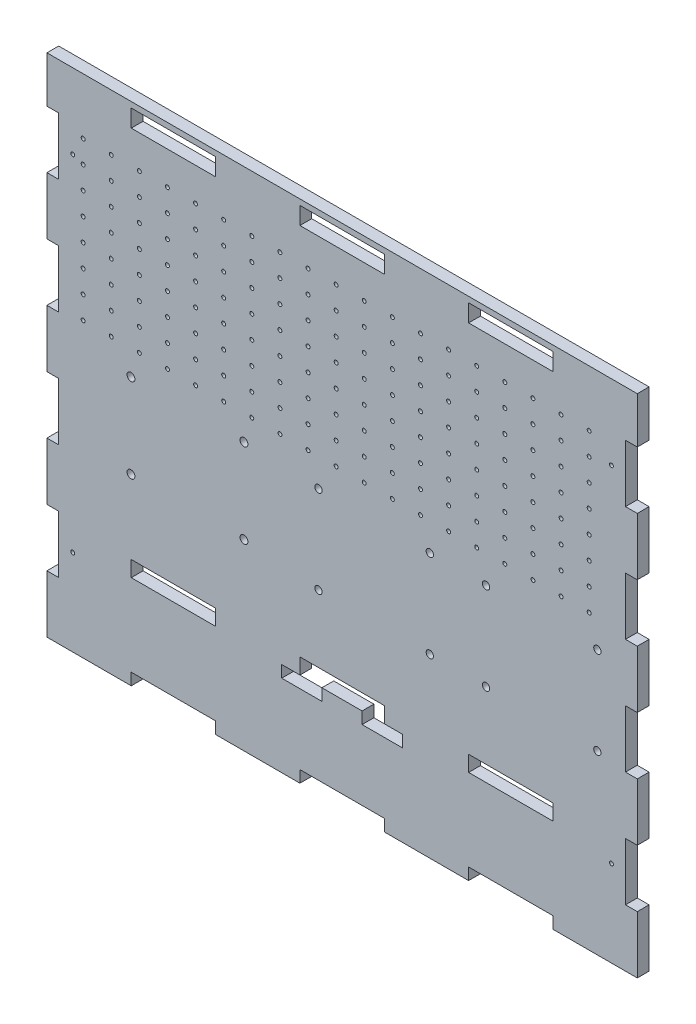
SolidWorks part; units mm, degrees
ref_plane "Front Plane" through (0, 0, 0) normal (0, 0, 1) x (1, 0, 0)
ref_plane "Top Plane" through (0, 0, 0) normal (0, 1, 0) x (1, 0, 0)
ref_plane "Right Plane" through (0, 0, 0) normal (1, 0, 0) x (0, 0, -1)
sketch "Sketch1" plane through (0, 0, 0) normal (0, 0, 1) x (1, 0, 0)
  line L1 (-127.8759, 139.2641) -> (138.8241, 139.2641)
  line L2 (-127.8759, 139.2641) -> (-127.8759, -84.2559)
  line L3 (-127.8759, -84.2559) -> (138.8241, -84.2559)
  line L4 (138.8241, 139.2641) -> (138.8241, -84.2559)
  dimension "D1" = 266.7
  dimension "D2" = 223.52
extrude "Boss-Extrude1" add sketch "Sketch1" along normal blind 5.334
sketch "Sketch2" plane through (0, 0, 5.334) normal (0, 0, 1) x (1, 0, 0)
  line L0 (-127.8759, -84.2559) -> (138.8241, -84.2559) construction
  line L1 (-89.7759, -84.2559) -> (-51.6759, -84.2559)
  line L2 (-89.7759, -84.2559) -> (-89.7759, -78.9219)
  line L3 (-89.7759, -78.9219) -> (-51.6759, -78.9219)
  line L4 (-51.6759, -84.2559) -> (-51.6759, -78.9219)
  line L5 (-89.7759, -78.9219) -> (-127.8759, -78.9219) construction
  line L6 (-13.5759, -84.2559) -> (24.5241, -84.2559)
  line L7 (-13.5759, -84.2559) -> (-13.5759, -78.9219)
  line L8 (-13.5759, -78.9219) -> (24.5241, -78.9219)
  line L9 (24.5241, -84.2559) -> (24.5241, -78.9219)
  line L10 (62.6241, -84.2559) -> (100.7241, -84.2559)
  line L11 (62.6241, -84.2559) -> (62.6241, -78.9219)
  line L12 (62.6241, -78.9219) -> (100.7241, -78.9219)
  line L13 (100.7241, -84.2559) -> (100.7241, -78.9219)
  line L14 (-127.8759, 139.2641) -> (-127.8759, -84.2559) construction
  line L15 (-51.6759, -78.9219) -> (-13.5759, -78.9219) construction
  line L16 (24.5241, -78.9219) -> (62.6241, -78.9219) construction
  line L17 (62.6241, -78.9219) -> (62.364, -79.7896) construction
  line L18 (100.7241, -78.9219) -> (138.8241, -78.9219) construction
  line L19 (138.8241, -84.2559) -> (138.8241, 139.2641) construction
  line L20 (-127.8759, 27.5041) -> (138.8241, 27.5041) construction
  line L21 (100.7241, 139.2641) -> (100.7241, 133.9301)
  line L22 (62.6241, 133.9301) -> (100.7241, 133.9301)
  line L23 (62.6241, 139.2641) -> (62.6241, 133.9301)
  line L24 (24.5241, 139.2641) -> (24.5241, 133.9301)
  line L25 (-13.5759, 133.9301) -> (24.5241, 133.9301)
  line L26 (-13.5759, 139.2641) -> (-13.5759, 133.9301)
  line L27 (-51.6759, 139.2641) -> (-51.6759, 133.9301)
  line L28 (-89.7759, 133.9301) -> (-51.6759, 133.9301)
  line L29 (-89.7759, 139.2641) -> (-89.7759, 133.9301)
  line L30 (62.6241, 139.2641) -> (100.7241, 139.2641)
  line L31 (-13.5759, 139.2641) -> (24.5241, 139.2641)
  line L32 (-89.7759, 139.2641) -> (-51.6759, 139.2641)
  dimension "D1" = 5.334
extrude "Cut-Extrude1" cut sketch "Sketch2" against normal through all
sketch "Sketch5" plane through (0, 0, 5.334) normal (0, 0, 1) x (1, 0, 0)
  line L0 (-51.6759, -34.8224) -> (-13.5759, -34.8224) construction
  line L1 (-89.7759, -34.8224) -> (-51.6759, -34.8224)
  line L2 (-89.7759, -34.8224) -> (-89.7759, -41.9344)
  line L3 (-89.7759, -41.9344) -> (-51.6759, -41.9344)
  line L4 (-51.6759, -34.8224) -> (-51.6759, -41.9344)
  line L5 (-13.5759, -34.8224) -> (24.5241, -34.8224)
  line L6 (-13.5759, -34.8224) -> (-13.5759, -41.9344)
  line L7 (-13.5759, -41.9344) -> (24.5241, -41.9344)
  line L8 (24.5241, -34.8224) -> (24.5241, -41.9344)
  line L9 (62.6241, -34.8224) -> (100.7241, -34.8224)
  line L10 (62.6241, -34.8224) -> (62.6241, -41.9344)
  line L11 (62.6241, -41.9344) -> (100.7241, -41.9344)
  line L12 (100.7241, -34.8224) -> (100.7241, -41.9344)
  line L13 (-51.6759, -41.9344) -> (-13.5759, -41.9344) construction
  line L14 (24.5241, -34.8224) -> (62.6241, -34.8224) construction
  line L15 (24.5241, -41.9344) -> (62.6241, -41.9344) construction
  line L16 (-89.7759, -34.8224) -> (-127.8759, -34.8224) construction
  line L17 (-127.8759, 139.2641) -> (-127.8759, -84.2559) construction
  line L18 (-89.7759, -41.9344) -> (-127.8759, -41.9344) construction
  line L19 (100.7241, -34.8224) -> (138.8241, -34.8224) construction
  line L20 (138.8241, -84.2559) -> (138.8241, 139.2641) construction
  line L21 (100.7241, -41.9344) -> (138.8241, -41.9344) construction
  dimension "D1" = 7.112
extrude "Cut-Extrude3" cut sketch "Sketch5" against normal through all
sketch "Sketch8" plane through (0, 0, 5.334) normal (0, 0, 1) x (1, 0, 0)
  line L0 (-13.5759, -41.9344) -> (24.5241, -41.9344) construction
  line L1 (-21.7977, -47.2684) -> (-3.6478, -47.2684)
  line L2 (-21.7977, -47.2684) -> (-21.7977, -41.9344)
  line L3 (-21.7977, -41.9344) -> (-3.6478, -41.9344)
  line L4 (-3.6478, -47.2684) -> (-3.6478, -41.9344)
  line L5 (-3.6478, -47.2684) -> (14.5022, -47.2684) construction
  line L6 (14.5022, -41.9344) -> (32.6521, -41.9344)
  line L7 (14.5022, -41.9344) -> (14.5022, -47.2684)
  line L8 (14.5022, -47.2684) -> (32.6521, -47.2684)
  line L9 (32.6521, -41.9344) -> (32.6521, -47.2684)
  line L10 (14.5022, -47.2684) -> (14.3218, -49.4005) construction
  line L11 (14.5022, -41.9344) -> (-3.6478, -41.9344) construction
  line L12 (62.6241, -34.8224) -> (62.6241, -41.9344) construction
  line L13 (-51.6759, -41.9344) -> (-51.6759, -34.8224) construction
  dimension "D1" = 5.334
  dimension "D2" = 29.972
  dimension "D3" = 29.8782
extrude "Cut-Extrude6" cut sketch "Sketch8" against normal through all
sketch "Sketch9" plane through (0, 0, 5.334) normal (0, 0, 1) x (1, 0, 0)
  line L0 (-111.5143, 118.9789) -> (-98.8143, 118.9789) construction
  line L1 (-111.5143, 108.8189) -> (-98.8143, 108.8189) construction
  line L2 (-111.5143, 98.6589) -> (-98.8143, 98.6589) construction
  line L3 (-111.5143, 88.4989) -> (-98.8143, 88.4989) construction
  line L4 (-111.5143, 78.3389) -> (-98.8143, 78.3389) construction
  line L5 (-111.5143, 68.1789) -> (-98.8143, 68.1789) construction
  line L6 (-111.5143, 58.0189) -> (-98.8143, 58.0189) construction
  line L7 (-111.5143, 47.8589) -> (-98.8143, 47.8589) construction
  line L8 (-111.5143, 118.9789) -> (-111.5143, 108.8189) construction
  circle A0 centre (-111.5143, 118.9789) radius 0.889
  circle A1 centre (-98.8143, 118.9789) radius 0.889
  circle A2 centre (-86.1143, 118.9789) radius 0.889
  circle A3 centre (-73.4143, 118.9789) radius 0.889
  circle A4 centre (-60.7143, 118.9789) radius 0.889
  circle A5 centre (-48.0143, 118.9789) radius 0.889
  circle A6 centre (-35.3143, 118.9789) radius 0.889
  circle A7 centre (-22.6143, 118.9789) radius 0.889
  circle A8 centre (-9.9143, 118.9789) radius 0.889
  circle A9 centre (2.7857, 118.9789) radius 0.889
  circle A10 centre (15.4857, 118.9789) radius 0.889
  circle A11 centre (28.1857, 118.9789) radius 0.889
  circle A12 centre (40.8857, 118.9789) radius 0.889
  circle A13 centre (53.5857, 118.9789) radius 0.889
  circle A14 centre (66.2857, 118.9789) radius 0.889
  circle A15 centre (78.9857, 118.9789) radius 0.889
  circle A16 centre (91.6857, 118.9789) radius 0.889
  circle A17 centre (104.3857, 118.9789) radius 0.889
  circle A18 centre (117.0857, 118.9789) radius 0.889
  circle A19 centre (-111.5143, 108.8189) radius 0.889
  circle A20 centre (-98.8143, 108.8189) radius 0.889
  circle A21 centre (-86.1143, 108.8189) radius 0.889
  circle A22 centre (-73.4143, 108.8189) radius 0.889
  circle A23 centre (-60.7143, 108.8189) radius 0.889
  circle A24 centre (-48.0143, 108.8189) radius 0.889
  circle A25 centre (-35.3143, 108.8189) radius 0.889
  circle A26 centre (-22.6143, 108.8189) radius 0.889
  circle A27 centre (-9.9143, 108.8189) radius 0.889
  circle A28 centre (2.7857, 108.8189) radius 0.889
  circle A29 centre (15.4857, 108.8189) radius 0.889
  circle A30 centre (28.1857, 108.8189) radius 0.889
  circle A31 centre (40.8857, 108.8189) radius 0.889
  circle A32 centre (53.5857, 108.8189) radius 0.889
  circle A33 centre (66.2857, 108.8189) radius 0.889
  circle A34 centre (78.9857, 108.8189) radius 0.889
  circle A35 centre (91.6857, 108.8189) radius 0.889
  circle A36 centre (104.3857, 108.8189) radius 0.889
  circle A37 centre (117.0857, 108.8189) radius 0.889
  circle A38 centre (-111.5143, 98.6589) radius 0.889
  circle A39 centre (-98.8143, 98.6589) radius 0.889
  circle A40 centre (-86.1143, 98.6589) radius 0.889
  circle A41 centre (-73.4143, 98.6589) radius 0.889
  circle A42 centre (-60.7143, 98.6589) radius 0.889
  circle A43 centre (-48.0143, 98.6589) radius 0.889
  circle A44 centre (-35.3143, 98.6589) radius 0.889
  circle A45 centre (-22.6143, 98.6589) radius 0.889
  circle A46 centre (-9.9143, 98.6589) radius 0.889
  circle A47 centre (2.7857, 98.6589) radius 0.889
  circle A48 centre (15.4857, 98.6589) radius 0.889
  circle A49 centre (28.1857, 98.6589) radius 0.889
  circle A50 centre (40.8857, 98.6589) radius 0.889
  circle A51 centre (53.5857, 98.6589) radius 0.889
  circle A52 centre (66.2857, 98.6589) radius 0.889
  circle A53 centre (78.9857, 98.6589) radius 0.889
  circle A54 centre (91.6857, 98.6589) radius 0.889
  circle A55 centre (104.3857, 98.6589) radius 0.889
  circle A56 centre (117.0857, 98.6589) radius 0.889
  circle A57 centre (-111.5143, 88.4989) radius 0.889
  circle A58 centre (-98.8143, 88.4989) radius 0.889
  circle A59 centre (-86.1143, 88.4989) radius 0.889
  circle A60 centre (-73.4143, 88.4989) radius 0.889
  circle A61 centre (-60.7143, 88.4989) radius 0.889
  circle A62 centre (-48.0143, 88.4989) radius 0.889
  circle A63 centre (-35.3143, 88.4989) radius 0.889
  circle A64 centre (-22.6143, 88.4989) radius 0.889
  circle A65 centre (-9.9143, 88.4989) radius 0.889
  circle A66 centre (2.7857, 88.4989) radius 0.889
  circle A67 centre (15.4857, 88.4989) radius 0.889
  circle A68 centre (28.1857, 88.4989) radius 0.889
  circle A69 centre (40.8857, 88.4989) radius 0.889
  circle A70 centre (53.5857, 88.4989) radius 0.889
  circle A71 centre (66.2857, 88.4989) radius 0.889
  circle A72 centre (78.9857, 88.4989) radius 0.889
  circle A73 centre (91.6857, 88.4989) radius 0.889
  circle A74 centre (104.3857, 88.4989) radius 0.889
  circle A75 centre (117.0857, 88.4989) radius 0.889
  circle A76 centre (-111.5143, 78.3389) radius 0.889
  circle A77 centre (-98.8143, 78.3389) radius 0.889
  circle A78 centre (-86.1143, 78.3389) radius 0.889
  circle A79 centre (-73.4143, 78.3389) radius 0.889
  circle A80 centre (-60.7143, 78.3389) radius 0.889
  circle A81 centre (-48.0143, 78.3389) radius 0.889
  circle A82 centre (-35.3143, 78.3389) radius 0.889
  circle A83 centre (-22.6143, 78.3389) radius 0.889
  circle A84 centre (-9.9143, 78.3389) radius 0.889
  circle A85 centre (2.7857, 78.3389) radius 0.889
  circle A86 centre (15.4857, 78.3389) radius 0.889
  circle A87 centre (28.1857, 78.3389) radius 0.889
  circle A88 centre (40.8857, 78.3389) radius 0.889
  circle A89 centre (53.5857, 78.3389) radius 0.889
  circle A90 centre (66.2857, 78.3389) radius 0.889
  circle A91 centre (78.9857, 78.3389) radius 0.889
  circle A92 centre (91.6857, 78.3389) radius 0.889
  circle A93 centre (104.3857, 78.3389) radius 0.889
  circle A94 centre (117.0857, 78.3389) radius 0.889
  circle A95 centre (-111.5143, 68.1789) radius 0.889
  circle A96 centre (-98.8143, 68.1789) radius 0.889
  circle A97 centre (-86.1143, 68.1789) radius 0.889
  circle A98 centre (-73.4143, 68.1789) radius 0.889
  circle A99 centre (-60.7143, 68.1789) radius 0.889
  circle A100 centre (-48.0143, 68.1789) radius 0.889
  circle A101 centre (-35.3143, 68.1789) radius 0.889
  circle A102 centre (-22.6143, 68.1789) radius 0.889
  circle A103 centre (-9.9143, 68.1789) radius 0.889
  circle A104 centre (2.7857, 68.1789) radius 0.889
  circle A105 centre (15.4857, 68.1789) radius 0.889
  circle A106 centre (28.1857, 68.1789) radius 0.889
  circle A107 centre (40.8857, 68.1789) radius 0.889
  circle A108 centre (53.5857, 68.1789) radius 0.889
  circle A109 centre (66.2857, 68.1789) radius 0.889
  circle A110 centre (78.9857, 68.1789) radius 0.889
  circle A111 centre (91.6857, 68.1789) radius 0.889
  circle A112 centre (104.3857, 68.1789) radius 0.889
  circle A113 centre (117.0857, 68.1789) radius 0.889
  circle A114 centre (-111.5143, 58.0189) radius 0.889
  circle A115 centre (-98.8143, 58.0189) radius 0.889
  circle A116 centre (-86.1143, 58.0189) radius 0.889
  circle A117 centre (-73.4143, 58.0189) radius 0.889
  circle A118 centre (-60.7143, 58.0189) radius 0.889
  circle A119 centre (-48.0143, 58.0189) radius 0.889
  circle A120 centre (-35.3143, 58.0189) radius 0.889
  circle A121 centre (-22.6143, 58.0189) radius 0.889
  circle A122 centre (-9.9143, 58.0189) radius 0.889
  circle A123 centre (2.7857, 58.0189) radius 0.889
  circle A124 centre (15.4857, 58.0189) radius 0.889
  circle A125 centre (28.1857, 58.0189) radius 0.889
  circle A126 centre (40.8857, 58.0189) radius 0.889
  circle A127 centre (53.5857, 58.0189) radius 0.889
  circle A128 centre (66.2857, 58.0189) radius 0.889
  circle A129 centre (78.9857, 58.0189) radius 0.889
  circle A130 centre (91.6857, 58.0189) radius 0.889
  circle A131 centre (104.3857, 58.0189) radius 0.889
  circle A132 centre (117.0857, 58.0189) radius 0.889
  circle A133 centre (-111.5143, 47.8589) radius 0.889
  circle A134 centre (-98.8143, 47.8589) radius 0.889
  circle A135 centre (-86.1143, 47.8589) radius 0.889
  circle A136 centre (-73.4143, 47.8589) radius 0.889
  circle A137 centre (-60.7143, 47.8589) radius 0.889
  circle A138 centre (-48.0143, 47.8589) radius 0.889
  circle A139 centre (-35.3143, 47.8589) radius 0.889
  circle A140 centre (-22.6143, 47.8589) radius 0.889
  circle A141 centre (-9.9143, 47.8589) radius 0.889
  circle A142 centre (2.7857, 47.8589) radius 0.889
  circle A143 centre (15.4857, 47.8589) radius 0.889
  circle A144 centre (28.1857, 47.8589) radius 0.889
  circle A145 centre (40.8857, 47.8589) radius 0.889
  circle A146 centre (53.5857, 47.8589) radius 0.889
  circle A147 centre (66.2857, 47.8589) radius 0.889
  circle A148 centre (78.9857, 47.8589) radius 0.889
  circle A149 centre (91.6857, 47.8589) radius 0.889
  circle A150 centre (104.3857, 47.8589) radius 0.889
  circle A151 centre (117.0857, 47.8589) radius 0.889
  dimension "D1" = 19
  dimension "D5" = 1.778
  dimension "D2" = 12.7
  dimension "D4" = 10.16
  dimension "D3" = 8
extrude "Cut-Extrude7" cut sketch "Sketch9" against normal through all
sketch "Sketch10" plane through (0, 139.2641, 0) normal (0, 1, 0) x (1, 0, 0)
  line L0 (-13.5759, -5.334) -> (-51.6759, -5.334) construction
  line L1 (-51.6759, 0) -> (-13.5759, 0)
  line L2 (-51.6759, 0) -> (-51.6759, -5.334)
  line L3 (-51.6759, -5.334) -> (-13.5759, -5.334)
  line L4 (-13.5759, 0) -> (-13.5759, -5.334)
extrude "Boss-Extrude2" add sketch "Sketch10" along normal blind 10.16
sketch "Sketch12" plane through (-51.6759, 0, 0) normal (-1, 0, 0) x (0, 0, 1)
  line L0 (0, 133.9301) -> (0, 149.4241) construction
  line L1 (5.334, 149.4241) -> (0, 149.4241)
  line L2 (5.334, 149.4241) -> (5.334, 141.8041)
  line L3 (5.334, 141.8041) -> (0, 141.8041)
  line L4 (0, 149.4241) -> (0, 141.8041)
  dimension "D1" = 7.62
extrude "Boss-Extrude3" add sketch "Sketch12" along normal blind 76.2 and the other way blind 190.5
sketch "Sketch13" plane through (0, 139.2641, 0) normal (0, 1, 0) x (1, 0, 0)
  line L1 (-127.8759, 0) -> (-89.7759, 0)
  line L2 (-127.8759, 0) -> (-127.8759, -5.334)
  line L3 (-127.8759, -5.334) -> (-89.7759, -5.334)
  line L4 (-89.7759, 0) -> (-89.7759, -5.334)
extrude "Boss-Extrude4" add sketch "Sketch13" along normal blind 2.54
sketch "Sketch14" plane through (0, 139.2641, 0) normal (0, 1, 0) x (1, 0, 0)
  line L1 (24.5241, 0) -> (62.6241, 0)
  line L2 (24.5241, 0) -> (24.5241, -5.334)
  line L3 (24.5241, -5.334) -> (62.6241, -5.334)
  line L4 (62.6241, 0) -> (62.6241, -5.334)
extrude "Boss-Extrude5" add sketch "Sketch14" along normal blind 2.54
sketch "Sketch15" plane through (0, 139.2641, 0) normal (0, 1, 0) x (1, 0, 0)
  line L1 (100.7241, 0) -> (138.8241, 0)
  line L2 (100.7241, 0) -> (100.7241, -5.334)
  line L3 (100.7241, -5.334) -> (138.8241, -5.334)
  line L4 (138.8241, 0) -> (138.8241, -5.334)
extrude "Boss-Extrude6" add sketch "Sketch15" along normal blind 2.54
sketch "Sketch16" plane through (0, 0, 5.334) normal (0, 0, 1) x (1, 0, 0)
  line L0 (-127.8759, 149.4241) -> (-127.8759, -84.2559) construction
  line L1 (-127.8759, -32.327) -> (-122.5419, -32.327)
  line L2 (-127.8759, -32.327) -> (-127.8759, -58.2914)
  line L3 (-127.8759, -58.2914) -> (-122.5419, -58.2914)
  line L4 (-122.5419, -32.327) -> (-122.5419, -58.2914)
  line L5 (-122.5419, -32.327) -> (-122.5419, -6.3625) construction
  line L6 (-127.8759, 19.6019) -> (-122.5419, 19.6019)
  line L7 (-122.5419, -58.2914) -> (-122.5419, -84.2559) construction
  line L8 (-127.8759, -84.2559) -> (-89.7759, -84.2559) construction
  line L9 (-127.8759, 19.6019) -> (-127.8759, -6.3625)
  line L10 (-127.8759, -6.3625) -> (-122.5419, -6.3625)
  line L11 (-122.5419, 19.6019) -> (-122.5419, -6.3625)
  line L12 (-122.5419, 19.6019) -> (-122.5419, 45.5664) construction
  line L13 (5.4741, -78.9219) -> (5.4741, 149.4241) construction
  line L14 (-127.8759, 71.5308) -> (-122.5419, 71.5308)
  line L15 (-127.8759, 71.5308) -> (-127.8759, 45.5664)
  line L16 (-127.8759, 45.5664) -> (-122.5419, 45.5664)
  line L17 (-122.5419, 71.5308) -> (-122.5419, 45.5664)
  line L18 (-122.5419, 71.5308) -> (-122.5419, 97.4953) construction
  line L19 (24.5241, -78.9219) -> (-13.5759, -78.9219) construction
  line L20 (-127.8759, 97.4953) -> (-122.5419, 97.4953)
  line L21 (-127.8759, 97.4953) -> (-127.8759, 123.4597)
  line L22 (-127.8759, 123.4597) -> (-122.5419, 123.4597)
  line L23 (-122.5419, 97.4953) -> (-122.5419, 123.4597)
  line L24 (-122.5419, 123.4597) -> (-122.5419, 149.4241) construction
  line L25 (-127.8759, 149.4241) -> (138.8241, 149.4241) construction
  line L26 (133.4901, 123.4597) -> (133.4901, 149.4241) construction
  line L27 (133.4901, 71.5308) -> (133.4901, 97.4953) construction
  line L28 (133.4901, 19.6019) -> (133.4901, 45.5664) construction
  line L29 (133.4901, -58.2914) -> (133.4901, -84.2559) construction
  line L30 (133.4901, -32.327) -> (133.4901, -6.3625) construction
  line L31 (133.4901, 97.4953) -> (133.4901, 123.4597)
  line L32 (138.8241, 123.4597) -> (133.4901, 123.4597)
  line L33 (138.8241, 97.4953) -> (138.8241, 123.4597)
  line L34 (138.8241, 97.4953) -> (133.4901, 97.4953)
  line L35 (133.4901, 71.5308) -> (133.4901, 45.5664)
  line L36 (138.8241, 45.5664) -> (133.4901, 45.5664)
  line L37 (138.8241, 71.5308) -> (138.8241, 45.5664)
  line L38 (138.8241, 71.5308) -> (133.4901, 71.5308)
  line L39 (133.4901, 19.6019) -> (133.4901, -6.3625)
  line L40 (138.8241, -6.3625) -> (133.4901, -6.3625)
  line L41 (138.8241, 19.6019) -> (138.8241, -6.3625)
  line L42 (138.8241, 19.6019) -> (133.4901, 19.6019)
  line L43 (133.4901, -32.327) -> (133.4901, -58.2914)
  line L44 (138.8241, -58.2914) -> (133.4901, -58.2914)
  line L45 (138.8241, -32.327) -> (138.8241, -58.2914)
  line L46 (138.8241, -32.327) -> (133.4901, -32.327)
  dimension "D1" = 5.334
extrude "Cut-Extrude9" cut sketch "Sketch16" against normal through all
sketch "Sketch17" plane through (0, 0, 5.334) normal (0, 0, 1) x (1, 0, 0)
  line L1 (133.4901, 71.5308) -> (133.4901, 45.5664) construction
  circle A0 centre (120.7901, 35.1589) radius 1.651
  circle A1 centre (117.0857, 47.8589) radius 0.889 construction
  circle A2 centre (70.4981, 35.1589) radius 1.651
  circle A3 centre (70.4981, -4.4651) radius 1.651
  circle A4 centre (120.7901, -4.4651) radius 1.651
  circle A5 centre (45.0981, 35.1589) radius 1.651
  circle A6 centre (-5.1939, 35.1589) radius 1.651
  circle A7 centre (-5.1939, -4.4651) radius 1.651
  circle A8 centre (45.0981, -4.4651) radius 1.651
  dimension "D1" = 12.7
  dimension "D2" = 12.7
  dimension "D3" = 2
  dimension "D4" = 2
  dimension "D5" = 2
  dimension "D6" = 2
  dimension "D7" = 2
extrude "Cut-Extrude10" cut sketch "Sketch17" against normal through all
sketch "Sketch18" plane through (0, 0, 5.334) normal (0, 0, 1) x (1, 0, 0)
  line L0 (133.4901, 123.4597) -> (133.4901, 97.4953) construction
  line L1 (133.4901, 110.4775) -> (-122.5419, 110.4775) construction
  line L2 (-122.5419, 97.4953) -> (-122.5419, 123.4597) construction
  line L3 (-122.5419, -45.3092) -> (133.4901, -45.3092) construction
  line L4 (-122.5419, -58.2914) -> (-122.5419, -32.327) construction
  line L5 (133.4901, -32.327) -> (133.4901, -58.2914) construction
  line L6 (138.8241, 32.5841) -> (-127.8759, 32.5841) construction
  line L7 (138.8241, 19.6019) -> (138.8241, 45.5664) construction
  line L8 (-127.8759, 45.5664) -> (-127.8759, 19.6019) construction
  line L9 (5.4741, 149.4241) -> (5.4741, -78.9219) construction
  line L10 (-127.8759, 149.4241) -> (138.8241, 149.4241) construction
  line L11 (24.5241, -78.9219) -> (-13.5759, -78.9219) construction
  circle A0 centre (127.1401, 110.4775) radius 0.889
  circle A1 centre (-116.1919, 110.4775) radius 0.889
  circle A2 centre (-116.1919, -45.3092) radius 0.889
  circle A3 centre (127.1401, -45.3092) radius 0.889
  dimension "D3" = 1.778
  dimension "D1" = 0
  dimension "D2" = 6.35
extrude "Cut-Extrude11" cut sketch "Sketch18" against normal through all
sketch "Sketch19" plane through (0, 0, 0) normal (0, 0, -1) x (-1, 0, 0)
  circle A0 centre (89.9029, 36.5559) radius 1.778 construction
  circle A1 centre (89.9029, -1.5441) radius 1.778 construction
  circle A2 centre (38.8489, -1.5441) radius 1.778 construction
  circle A3 centre (38.8489, 36.5559) radius 1.778 construction
  circle A4 centre (89.9029, 36.5559) radius 1.778
  circle A5 centre (89.9029, -1.5441) radius 1.778
  circle A6 centre (38.8489, -1.5441) radius 1.778
  circle A7 centre (38.8489, 36.5559) radius 1.778
extrude "Cut-Extrude12" cut sketch "Sketch19" against normal through all
sketch "Sketch20" plane through (0, 0, 5.334) normal (0, 0, 1) x (1, 0, 0)
  line L0 (138.8241, 123.4597) -> (138.8241, 149.4241) construction
  line L1 (-127.8759, 149.4241) -> (138.8241, 149.4241)
  line L2 (-127.8759, 149.4241) -> (-127.8759, 144.3441)
  line L3 (-127.8759, 144.3441) -> (138.8241, 144.3441)
  line L4 (138.8241, 149.4241) -> (138.8241, 144.3441)
  dimension "D1" = 5.08
extrude "Cut-Extrude13" cut sketch "Sketch20" against normal through all
equation "\"MDF\"= .21in"
equation "\"Foamcore\"= .13in"
equation "\"Gmaterial\"= \"MDF\""
equation "\"D1@Boss-Extrude1\"=\"MDF\""
equation "\"D1@Sketch2\"=\"MDF\""
equation "\"D1@Sketch5\"=\"MDF\"+0.07"
equation "\"D1@Sketch8\"=\"MDF\""
equation "\"D1@Sketch16\"=\"MDF\""
